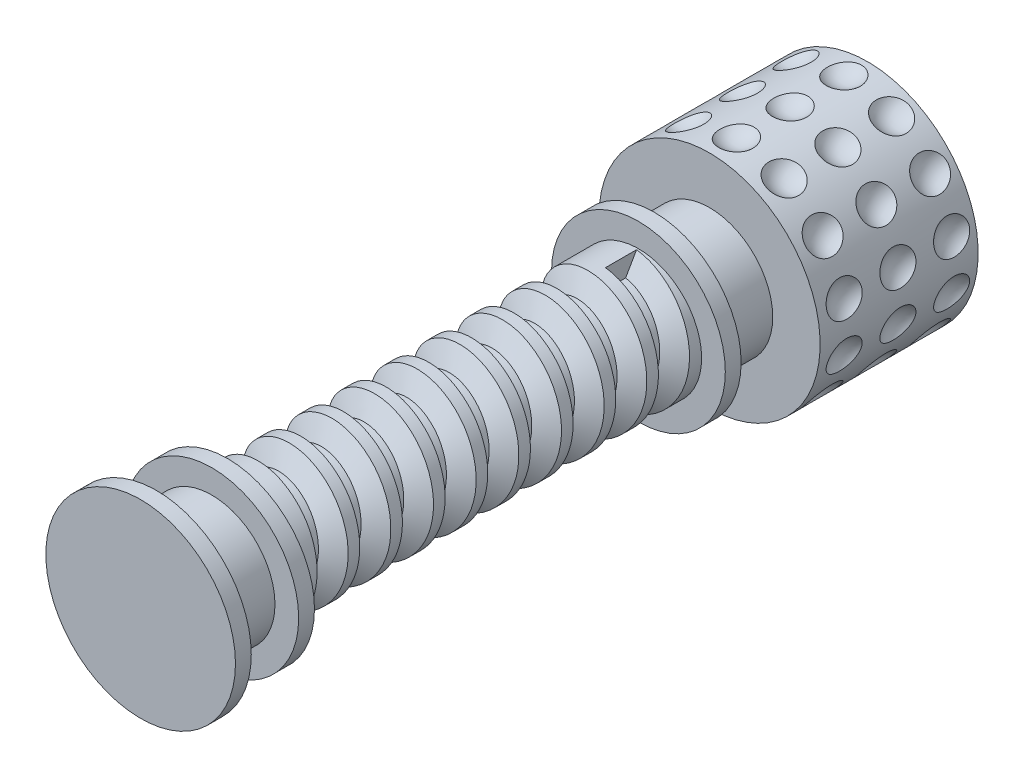
SolidWorks part; units mm, degrees
ref_plane "Front Plane" through (0, 0, 0) normal (0, 0, 1) x (1, 0, 0)
ref_plane "Top Plane" through (0, 0, 0) normal (0, 1, 0) x (1, 0, 0)
ref_plane "Right Plane" through (0, 0, 0) normal (1, 0, 0) x (0, 0, -1)
ref_axis "Axis1" through (0, 0, -12.3) along (0, 0, 1)
sketch "Sketch2" plane through (0, 0, 0) normal (0, 0, 1) x (1, 0, 0)
  circle A0 centre (0, 0) radius 4
  dimension "D1" = 8
extrude "Boss-Extrude1" add sketch "Sketch2" along normal blind 36
sketch "Sketch3" plane through (0, 0, 0) normal (0, 0, -1) x (-1, 0, 0)
  circle A0 centre (0, 0) radius 7
  dimension "D1" = 14
extrude "Boss-Extrude2" add sketch "Sketch3" along normal blind 10
sketch "Sketch4" plane through (0, 0, 0) normal (0, 0, 1) x (1, 0, 0)
  circle A0 centre (0, 0) radius 5.5
  dimension "D1" = 11
extrude "Boss-Extrude5" add sketch "Sketch4" along normal blind 1 from offset 3.5
sketch "Sketch6" plane through (0, 0, 0) normal (0, 0, 1) x (1, 0, 0)
  circle A0 centre (0, 0) radius 5.5
  dimension "D1" = 11
extrude "Boss-Extrude6" add sketch "Sketch6" against normal blind 1 from offset 31.5
sketch "Sketch7" plane through (0, 0, 0) normal (0, 0, 1) x (1, 0, 0)
  circle A0 centre (0, 0) radius 6
  dimension "D1" = 12
extrude "Boss-Extrude7" add sketch "Sketch7" along normal blind 1 from offset 35
sketch "Sketch8" plane through (0, 0, 4.5) normal (0, 0, 1) x (1, 0, 0)
  circle A0 centre (0, 0) radius 4
curve "Helix/Spiral1" pitch 2.7 height 24 radius 4 left hand yes centre (0, 0, 4.5) axis (0, 0, 1) start towards (0, 1, 0)
sketch "Sketch9" plane through (0, 0, 0) normal (1, 0, 0) x (0, 0, -1)
  line L0 (-4.5, 4.2) -> (-5.3083, 2.8)
  line L1 (-5.8917, 2.8) -> (-6.7, 4.2)
  line L2 (-6.7, 4.2) -> (-4.5, 4.2)
  line L3 (-5.3083, 2.8) -> (-5.8917, 2.8)
  line L4 (-4.5, 5.5) -> (-4.5, -5.5) construction
  dimension "D1" = 60
  dimension "D2" = 2.2
  dimension "D3" = 1.4
  dimension "D4" = 4.2
sweep "Cut-Sweep3" cut profiles "Sketch9" path "Helix/Spiral1"
sketch "Sketch10" plane through (0, 0, 0) normal (1, 0, 0) x (0, 0, -1)
  line L1 (10, -7) -> (10, 7) construction
  line L2 (10, 8) -> (7, 8)
  arc A0 (7, 8) -> (10, 8) centre (8.5, 8) ccw
  dimension "D1" = 3
  dimension "D2" = 8
  dimension "D3" = 1.5
revolve "Cut-Revolve1" cut sketch "Sketch10" angle 360 about L2
pattern_circular "CirPattern1" count 14 over 360 about axis through (0, 0, -10) along (0, 0, -1) of "Cut-Revolve1"
pattern_linear "LPattern1" count 3 spacing 3.4 along (0, 0, 1) of "CirPattern1"
sketch "Sketch11" plane through (0, 0, -10) normal (0, 0, -1) x (-1, 0, 0)
  circle A0 centre (0, 0) radius 4
  dimension "D1" = 8
extrude "Cut-Extrude1" cut sketch "Sketch11" against normal blind 8
fillet "Fillet1" radius 4 1 edges at (-4, 0, -2)
